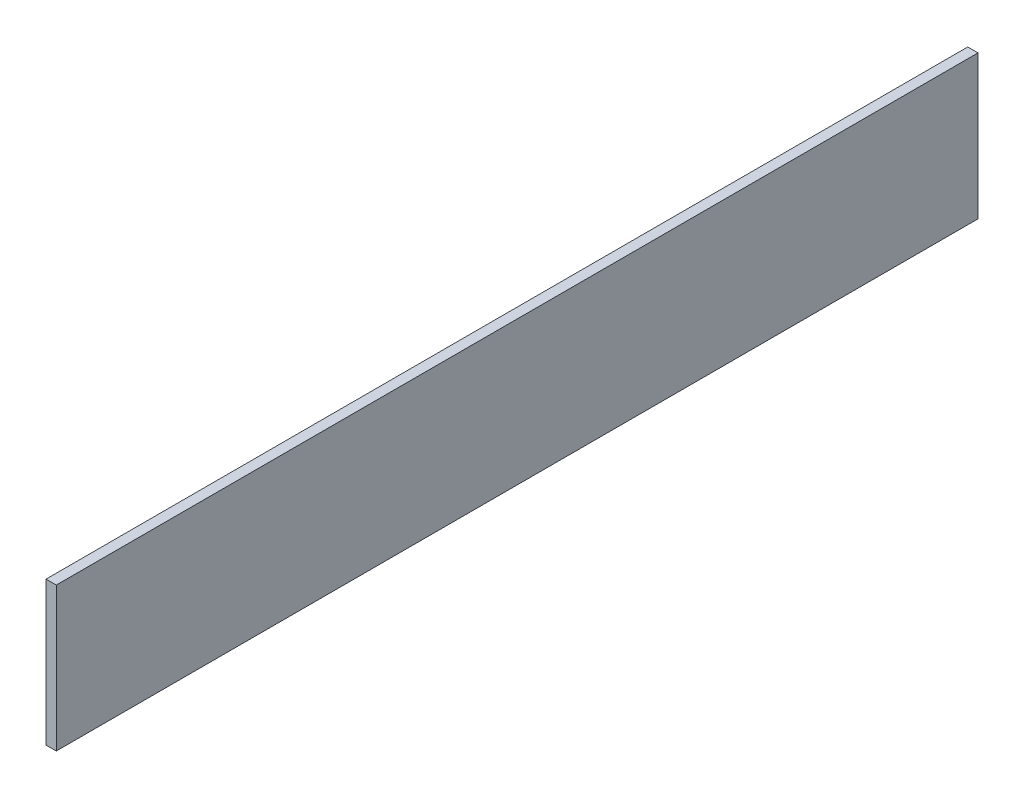
SolidWorks part; units mm, degrees
ref_plane "Plan de face" through (0, 0, 0) normal (0, 0, 1) x (1, 0, 0)
ref_plane "Plan de dessus" through (0, 0, 0) normal (0, 1, 0) x (1, 0, 0)
ref_plane "Plan de droite" through (0, 0, 0) normal (1, 0, 0) x (0, 0, -1)
sketch "Esquisse1" plane through (0, 0, 0) normal (1, 0, 0) x (0, 0, -1)
  line L1 (-285, 44.45) -> (285, 44.45)
  line L2 (-285, 44.45) -> (-285, -44.45)
  line L3 (-285, -44.45) -> (285, -44.45)
  line L4 (285, 44.45) -> (285, -44.45)
  point P4 (0, 44.45)
  point P6 (285, 0)
  dimension "D1" = 570
  dimension "D2" = 88.9
extrude "Boss.-Extru.1" add sketch "Esquisse1" along normal blind 6.35
